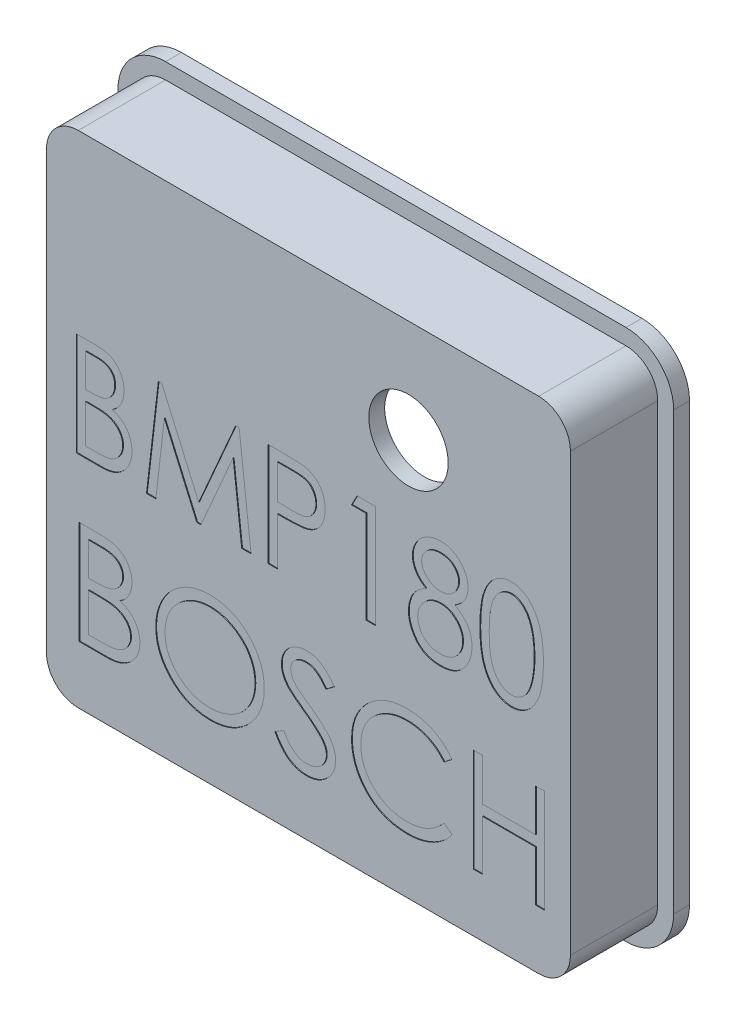
SolidWorks part; units mm, degrees
ref_plane "Спереди" through (0, 0, 0) normal (0, 0, 1) x (1, 0, 0)
ref_plane "Сверху" through (0, 0, 0) normal (0, 1, 0) x (1, 0, 0)
ref_plane "Справа" through (0, 0, 0) normal (1, 0, 0) x (0, 0, -1)
sketch "Эскиз1" plane through (0, 0, 0) normal (0, 0, 1) x (1, 0, 0)
  line L1 (0.3, 0) -> (3.2, 0)
  line L2 (0, -0.3) -> (0, -3.05)
  line L3 (0.3, -3.35) -> (3.2, -3.35)
  line L4 (3.5, -0.3) -> (3.5, -3.05)
  arc A0 (0, -3.05) -> (0.3, -3.35) centre (0.3, -3.05) ccw
  arc A1 (3.2, -3.35) -> (3.5, -3.05) centre (3.2, -3.05) ccw
  arc A2 (3.2, 0) -> (3.5, -0.3) centre (3.2, -0.3) cw
  arc A3 (0.3, 0) -> (0, -0.3) centre (0.3, -0.3) ccw
  point P7 (0, -3.35)
  point P12 (3.5, 0)
  point P15 (0, 0)
  dimension "D3" = 0.3
  dimension "D1" = 3.5
  dimension "D2" = 3.35
extrude "Бобышка-Вытянуть1" add sketch "Эскиз1" along normal blind 0.1
sketch "Эскиз2" plane through (0, 0, 0.1) normal (0, 0, 1) x (1, 0, 0)
  line L0 (0.3, -0.1) -> (3.2, -0.1)
  line L1 (0.3, 0) -> (3.2, 0) construction
  line L2 (0, -0.3) -> (0, -3.05) construction
  line L3 (0.3, -3.35) -> (3.2, -3.35) construction
  line L4 (3.5, -0.3) -> (3.5, -3.05) construction
  line L5 (3.4, -0.3) -> (3.4, -3.05)
  line L6 (0.3, -3.25) -> (3.2, -3.25)
  line L7 (0.1, -0.3) -> (0.1, -3.05)
  arc A0 (0, -3.05) -> (0.3, -3.35) centre (0.3, -3.05) ccw construction
  arc A1 (3.2, -3.35) -> (3.5, -3.05) centre (3.2, -3.05) ccw construction
  arc A2 (3.2, 0) -> (3.5, -0.3) centre (3.2, -0.3) cw construction
  arc A3 (0.3, 0) -> (0, -0.3) centre (0.3, -0.3) ccw construction
  arc A4 (3.2, -0.1) -> (3.4, -0.3) centre (3.2, -0.3) cw
  arc A5 (3.2, -3.25) -> (3.4, -3.05) centre (3.2, -3.05) ccw
  arc A6 (0.1, -3.05) -> (0.3, -3.25) centre (0.3, -3.05) ccw
  arc A7 (0.3, -0.1) -> (0.1, -0.3) centre (0.3, -0.3) ccw
  point P13 (0, 0)
  dimension "D1" = 0.3
  dimension "D2" = 0.1
extrude "Бобышка-Вытянуть2" add sketch "Эскиз2" along normal blind 0.55
shell "Оболочка2" thickness 0.1
sketch "Эскиз3" plane through (0, 0, 0) normal (0, 0, -1) x (-1, 0, 0)
  line L1 (-3.3007, -0.197) -> (-0.1965, -0.197)
  line L2 (-3.3007, -0.197) -> (-3.3007, -3.1532)
  line L3 (-3.3007, -3.1532) -> (-0.1965, -3.1532)
  line L4 (-0.1965, -0.197) -> (-0.1965, -3.1532)
extrude "Вырез-Вытянуть1" cut sketch "Эскиз3" against normal blind 0.11
sketch "Эскиз4" plane through (0, 0, 0.65) normal (0, 0, 1) x (1, 0, 0)
  line L0 (3.2, 0) -> (0.3, 0) construction
  line L1 (3.5, -3.05) -> (3.5, -0.3) construction
  circle A0 centre (2.38, -0.75) radius 0.25
  dimension "D1" = 0.5
  dimension "D2" = 0.75
  dimension "D3" = 1.12
extrude "Вырез-Вытянуть2" cut sketch "Эскиз4" against normal through all
sketch "Эскиз5" plane through (0, 0, 0.65) normal (0, 0, 1) x (1, 0, 0)
  text T0 "BMP180" font "Century Gothic" height 0.65
  text T1 "BOSCH" font "Century Gothic" height 0.65
extrude "Вырез-Вытянуть3" cut sketch "Эскиз5" against normal blind 0.005
